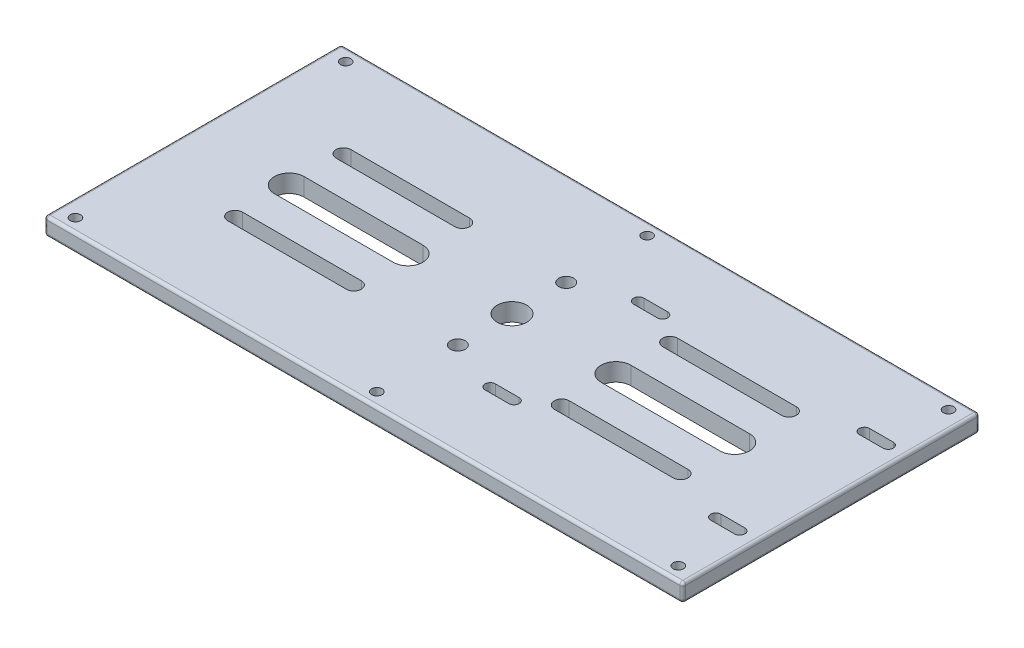
SolidWorks part; units mm, degrees
ref_plane "Front Plane" through (0, 0, 0) normal (0, 0, 1) x (1, 0, 0)
ref_plane "Top Plane" through (0, 0, 0) normal (0, 1, 0) x (1, 0, 0)
ref_plane "Right Plane" through (0, 0, 0) normal (1, 0, 0) x (0, 0, -1)
sketch "Sketch1" plane through (0, 0, 0) normal (0, 1, 0) x (1, 0, 0)
  line L0 (0, 0) -> (0, 18.25) construction
  line L1 (-107.5, 50) -> (107.5, 50)
  line L2 (-107.5, 50) -> (-107.5, -50)
  line L3 (-107.5, -50) -> (107.5, -50)
  line L4 (107.5, 50) -> (107.5, -50)
  line L5 (0, 0) -> (-19.3489, 0) construction
  line L6 (0, -5) -> (0, 5) construction
  line L7 (35, 5) -> (75, 5)
  line L9 (35, -5) -> (75, -5)
  line L11 (0, 20.75) -> (0, 15.75) construction
  line L12 (35, 15.75) -> (75, 15.75)
  line L14 (35, 20.75) -> (75, 20.75)
  line L32 (0, 0) -> (59.66, 0) construction
  line L33 (101.5, 45.5) -> (107.5, 45.5) construction
  line L34 (17.66, -23.25) -> (25.66, -23.25)
  line L35 (17.66, -26.75) -> (25.66, -26.75)
  line L36 (17.66, 26.75) -> (25.66, 26.75)
  line L38 (17.66, 23.25) -> (25.66, 23.25)
  line L39 (59.66, 0) -> (59.66, 13.4787) construction
  line L40 (101.66, -23.25) -> (93.66, -23.25)
  line L41 (101.66, -26.75) -> (93.66, -26.75)
  line L42 (101.66, 23.25) -> (93.66, 23.25)
  line L43 (101.66, 26.75) -> (93.66, 26.75)
  line L44 (35, -15.75) -> (75, -15.75)
  line L45 (35, -20.75) -> (75, -20.75)
  line L46 (-35, 15.75) -> (-75, 15.75)
  line L47 (-35, 20.75) -> (-75, 20.75)
  line L48 (-35, -5) -> (-75, -5)
  line L49 (-35, 5) -> (-75, 5)
  line L50 (-35, -15.75) -> (-75, -15.75)
  line L51 (-35, -20.75) -> (-75, -20.75)
  circle A0 centre (0, 0) radius 5
  circle A1 centre (0, 18.25) radius 2.5
  circle A2 centre (0, -18.25) radius 2.5
  circle A3 centre (101.5, 45.5) radius 1.75
  circle A7 centre (101.5, -45.5) radius 1.75
  circle A8 centre (-101.5, -45.5) radius 1.75
  circle A9 centre (-101.5, 45.5) radius 1.75
  arc A10 (35, 15.75) -> (35, 20.75) centre (35, 18.25) cw
  arc A11 (75, 15.75) -> (75, 20.75) centre (75, 18.25) ccw
  arc A12 (75, -5) -> (75, 5) centre (75, 0) ccw
  arc A13 (35, -5) -> (35, 5) centre (35, 0) cw
  arc A14 (25.66, 26.75) -> (25.66, 23.25) centre (25.66, 25) cw
  arc A15 (17.66, 23.25) -> (17.66, 26.75) centre (17.66, 25) cw
  arc A16 (17.66, -23.25) -> (17.66, -26.75) centre (17.66, -25) ccw
  arc A17 (25.66, -26.75) -> (25.66, -23.25) centre (25.66, -25) ccw
  arc A18 (93.66, -26.75) -> (93.66, -23.25) centre (93.66, -25) cw
  arc A19 (101.66, -23.25) -> (101.66, -26.75) centre (101.66, -25) cw
  arc A20 (101.66, 23.25) -> (101.66, 26.75) centre (101.66, 25) ccw
  arc A21 (93.66, 26.75) -> (93.66, 23.25) centre (93.66, 25) ccw
  arc A22 (35, -15.75) -> (35, -20.75) centre (35, -18.25) ccw
  arc A23 (75, -15.75) -> (75, -20.75) centre (75, -18.25) cw
  arc A24 (-35, 15.75) -> (-35, 20.75) centre (-35, 18.25) ccw
  arc A25 (-75, 15.75) -> (-75, 20.75) centre (-75, 18.25) cw
  arc A26 (-35, -5) -> (-35, 5) centre (-35, 0) ccw
  arc A27 (-75, -5) -> (-75, 5) centre (-75, 0) cw
  arc A28 (-75, -15.75) -> (-75, -20.75) centre (-75, -18.25) ccw
  arc A29 (-35, -15.75) -> (-35, -20.75) centre (-35, -18.25) cw
  circle A30 centre (0, 45.5) radius 1.75
  circle A31 centre (0, -45.5) radius 1.75
  point P4 (0, 50)
  point P6 (107.5, 0)
  point P21 (21.66, 26.75)
  point P60 (21.66, 23.25)
  dimension "D3" = 10
  dimension "D5" = 5
  dimension "D9" = 3.5
  dimension "D16" = 1.75
  dimension "D1" = 100
  dimension "D2" = 215
  dimension "D4" = 18.25
  dimension "D6" = 75
  dimension "D7" = 35
  dimension "D8" = 6
  dimension "D10" = 59.66
  dimension "D11" = 25
  dimension "D12" = 38
  dimension "D13" = 8
  dimension "D14" = 3.5
  dimension "D15" = 4.5
extrude "Boss-Extrude1" add sketch "Sketch1" along normal blind 6
fillet "Fillet1" radius 1 12 edges at (0, 6, -50) (0, 0, -50) (-107.5, 3, -50) (-107.5, 6, 0) (-107.5, 0, 0) (-107.5, 3, 50) (0, 6, 50) (0, 0, 50) (107.5, 3, 50) (107.5, 6, 0) (107.5, 3, -50) (107.5, 0, 0)
